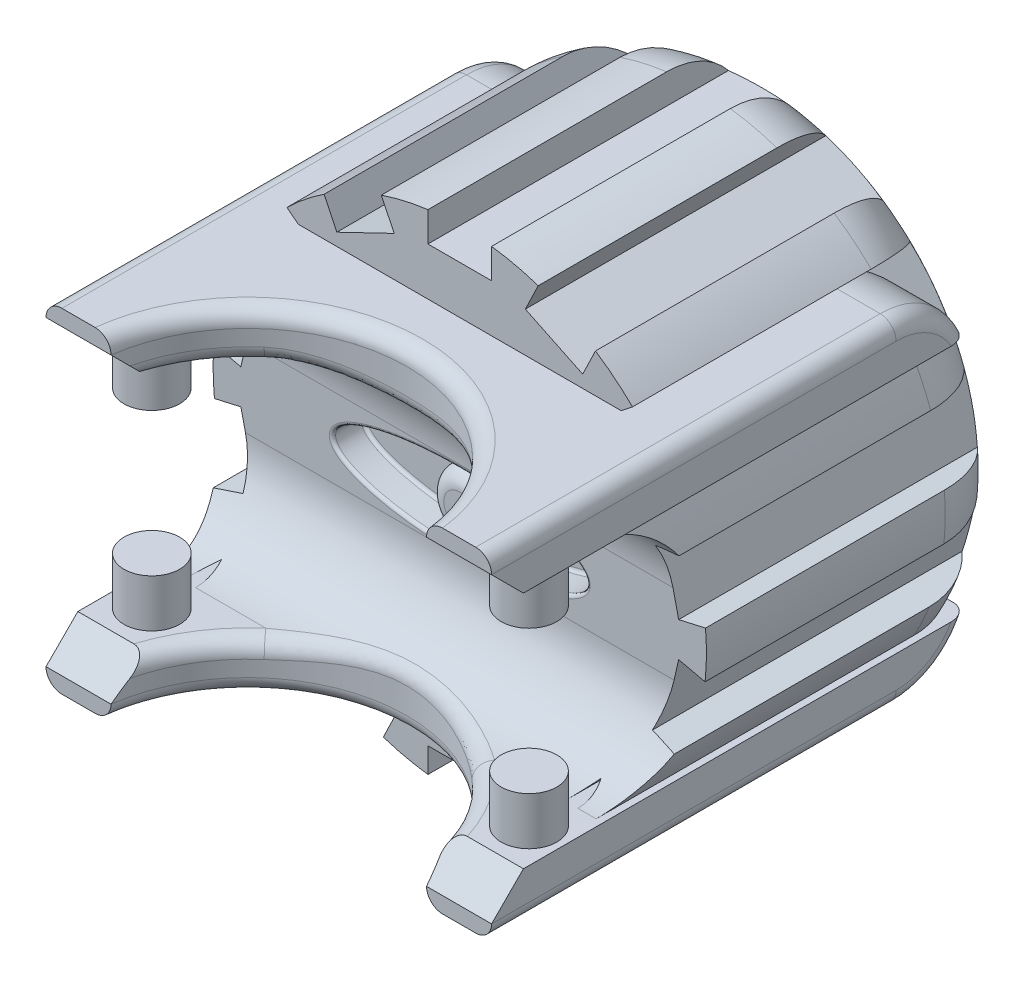
SolidWorks part; units mm, degrees
ref_plane "Front Plane" through (0, 0, 0) normal (0, 0, 1) x (1, 0, 0)
ref_plane "Top Plane" through (0, 0, 0) normal (0, 1, 0) x (1, 0, 0)
ref_plane "Right Plane" through (0, 0, 0) normal (1, 0, 0) x (0, 0, -1)
sketch "Sketch1" plane through (0, 0, 0) normal (0, 0, 1) x (1, 0, 0)
  circle A0 centre (0, 0) radius 15.5
  dimension "D1" = 31
extrude "Boss-Extrude1" add sketch "Sketch1" against normal blind 20
sketch "Sketch2" plane through (0, 0, -20) normal (0, 0, -1) x (-1, 0, 0)
  circle A0 centre (0, 0) radius 2.5
  dimension "D1" = 5
extrude "Boss-Extrude2" add sketch "Sketch2" along normal blind 3
fillet "Fillet1" radius 5 1 edges at (15.5, 0, -20)
sketch "Sketch3" plane through (0, 0, 0) normal (0, 0, 1) x (1, 0, 0)
  line L0 (0, 0) -> (0, 15.5) construction
  line L2 (-2, 17.5) -> (2, 17.5)
  line L3 (-2, 17.5) -> (-2, 13.5)
  line L4 (-2, 13.5) -> (2, 13.5)
  line L5 (2, 17.5) -> (2, 13.5)
  line L6 (-2, 17.5) -> (2, 13.5) construction
  line L7 (-2, 13.5) -> (2, 17.5) construction
  circle A0 centre (0, 0) radius 15.5 construction
  dimension "D1" = 4
  dimension "D2" = 4
extrude "Cut-Extrude1" cut sketch "Sketch3" against normal through all
pattern_circular "CirPattern1" count 14 over 360 about axis through (0, -0.1517, 0) along (0, 0, 1) of "Cut-Extrude1"
sketch "Sketch5" plane through (0, 0, -20) normal (0, 0, -1) x (-1, 0, 0)
  line L0 (0, 0) -> (0, 9) construction
  line L1 (0, 0) -> (17.6128, 0) construction
  line L2 (-14, -10.5) -> (14, -7.5) construction
  line L3 (-14, 7.5) -> (14, 7.5)
  line L4 (-14, 7.5) -> (-14, 10.5)
  line L5 (-14, 10.5) -> (14, 10.5)
  line L6 (14, 7.5) -> (14, 10.5)
  line L7 (-14, 7.5) -> (14, 10.5) construction
  line L8 (-14, 10.5) -> (14, 7.5) construction
  line L9 (-14, -7.5) -> (14, -10.5) construction
  line L10 (14, -7.5) -> (14, -10.5)
  line L11 (-14, -10.5) -> (14, -10.5)
  line L12 (-14, -7.5) -> (-14, -10.5)
  line L13 (-14, -7.5) -> (14, -7.5)
  dimension "D1" = 28
  dimension "D2" = 3
  dimension "D3" = 15
extrude "Boss-Extrude4" add sketch "Sketch5" against normal blind 30 from offset 2 offset against normal yes
fillet "Fillet2" radius 5 6 edges at (-11.8843, -10.5, -18) (-12, 10.5, -18) (12, 10.5, -18) (11.8843, -10.5, -18) (0, -7.5, 0) (0, 7.5, 0)
chamfer "Chamfer1" distance 2 angle 45 2 edges at (0, -7.5, 12) (0, 7.5, 12)
fillet "Fillet3" radius 1 8 edges at (14, 9.6833, -16.156) (-14, 9.6833, -16.156) (-14, -9.6833, -16.156) (14, -9.6833, -16.156) (14, 10.5, -0.7087) (-14, 10.5, -0.7087) (-14, -10.5, -0.7087) (14, -10.5, -0.7087)
sketch "Sketch6" plane through (0, 0, 0) normal (0, 0, 1) x (1, 0, 0)
  line L0 (0, 2.25) -> (0, 0) construction
  line L1 (0, 0) -> (8, 0) construction
  circle A0 centre (0, 0) radius 2
  ellipse E0 centre (0, 0) end of major axis (8, 0) minor radius 2.25
  dimension "D1" = 4
  dimension "D2" = 4.5
  dimension "D3" = 16
extrude "Cut-Extrude2" cut sketch "Sketch6" against normal blind 2
fillet "Fillet4" radius 1 1 edges at (2, 0, 0)
fillet "Fillet5" radius 0.2 1 edges at (8, 0, -2)
fillet "Fillet6" radius 0.2 1 edges at (8, 0, 0)
sketch "Sketch9" plane through (0, 0, 0) normal (0, 1, 0) x (1, 0, 0)
  line L0 (0, 0) -> (0, -13.33) construction
  circle A0 centre (0, -13.33) radius 10
  dimension "D1" = 20
  dimension "D2" = 13.33
extrude "Cut-Extrude3" cut sketch "Sketch9" against normal through all both and the other way through all
fillet "Fillet7" radius 1 8 edges at (7.8877, -7.5, 7.1831) (-7.8877, -7.5, 7.1831) (-7.8877, 7.5, 7.1831) (7.8877, 7.5, 7.1831) (0, 10.5, 3.33) (0, -10.5, 3.33) (0.6346, -7.22, 3.3502) (-0.6346, 7.22, 3.3502)
sketch "Sketch10" plane through (0, -7.5, 0) normal (0, 1, 0) x (1, 0, 0)
  line L1 (0, 0) -> (0, -17.494) construction
  line L3 (-14, -10) -> (-10.4838, -10) construction
  circle A0 centre (-11.85, -7.5) radius 1.75
  circle A1 centre (11.85, -7.5) radius 1.75
  dimension "D1" = 3.5
  dimension "D2" = 2.5
  dimension "D3" = 23.7
extrude "Boss-Extrude6" add sketch "Sketch10" along normal blind 3
mirror "Mirror1" about plane through (0, 0, 0) normal (0, 1, 0) of "Boss-Extrude6"
